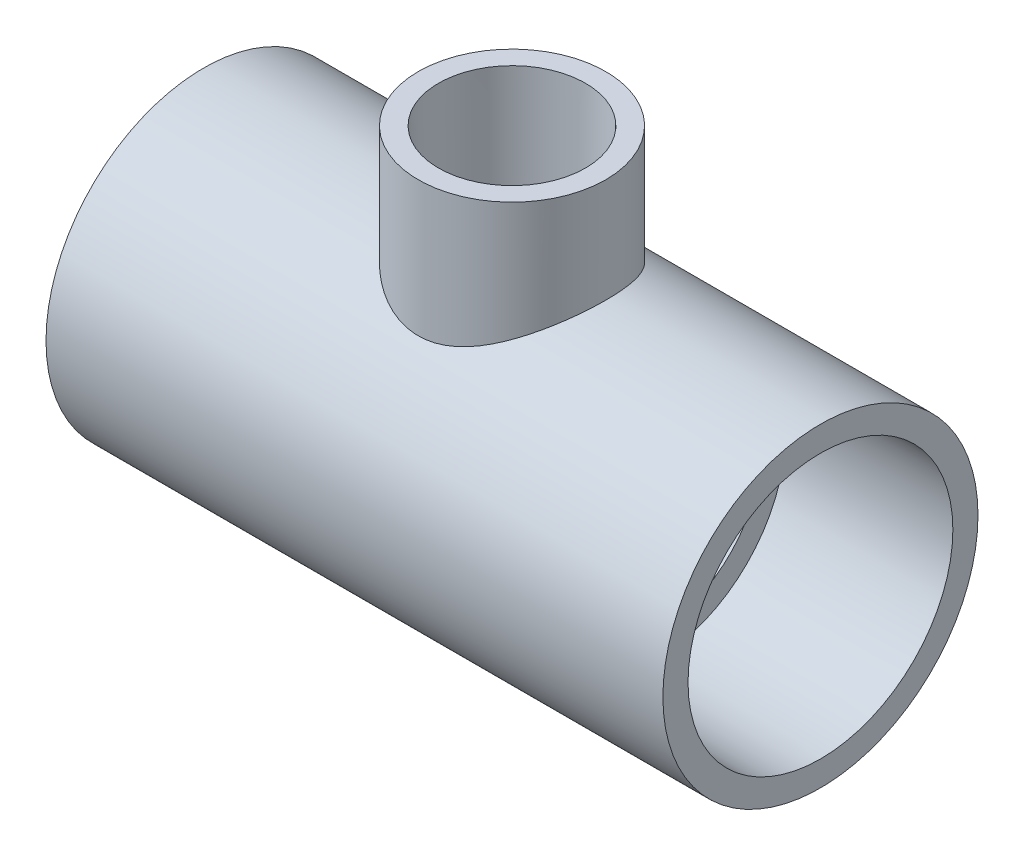
SolidWorks part; units mm, degrees
ref_plane "Front Plane" through (0, 0, 0) normal (0, 0, 1) x (1, 0, 0)
ref_plane "Top Plane" through (0, 0, 0) normal (0, 1, 0) x (1, 0, 0)
ref_plane "Right Plane" through (0, 0, 0) normal (1, 0, 0) x (0, 0, -1)
sketch "Sketch0" plane through (0, 0, 0) normal (0, 0, 1) x (1, 0, 0)
  line L0 (-70.612, 0) -> (0, 0) construction
  line L1 (0, 0) -> (0, 59.944) construction
  line L2 (-32.512, 0) -> (0, 0) construction
  line L3 (0, 0) -> (0, 31.369) construction
  line L4 (-70.612, 36.068) -> (-70.612, -36.068) construction
  line L5 (-32.512, 30.0863) -> (-70.612, 30.3149) construction
  line L6 (-32.512, 30.0863) -> (-32.512, -30.0863) construction
  line L7 (-32.512, -30.0863) -> (-70.612, -30.3149) construction
  line L8 (-70.612, 30.3149) -> (-70.612, -30.3149) construction
  line L9 (-21.463, 59.944) -> (21.463, 59.944) construction
  line L10 (-16.8275, 59.944) -> (16.8275, 59.944) construction
  line L11 (16.8275, 59.944) -> (16.637, 31.369) construction
  line L12 (16.637, 31.369) -> (-16.637, 31.369) construction
  line L13 (-16.637, 31.369) -> (-16.8275, 59.944) construction
  line L14 (-32.512, 24.6253) -> (-32.512, -24.6253) construction
  line L15 (-70.612, 0) -> (-32.512, 0) construction
  line L16 (0, 59.944) -> (0, 31.369) construction
  line L17 (0, 0) -> (32.512, 0) construction
  line L18 (-12.1539, 31.369) -> (12.1539, 31.369) construction
  line L19 (32.512, 0) -> (70.612, 0) construction
  dimension "D1" = 38.1
  dimension "H" = 70.612
  dimension "G" = 32.512
  dimension "M" = 72.136
  dimension "OD A" = 60.6298
  dimension "OD B" = 60.1726
  dimension "ID" = 49.2506
  dimension "H3" = 59.944
  dimension "G3" = 31.369
  dimension "M3" = 42.926
  dimension "D2" = 28.575
  dimension "OD A3" = 33.655
  dimension "OD B3" = 33.274
  dimension "ID3" = 24.3078
sketch "Sketch1" plane through (0, 0, 0) normal (0, 0, 1) x (1, 0, 0)
  line L0 (-70.612, 0) -> (0, 0) construction
  line L1 (-70.612, 0) -> (0, 0) construction
  line L2 (0, 0) -> (0, -36.068) construction
  line L3 (-70.612, -36.068) -> (-32.512, -36.068)
  line L4 (-70.612, -36.068) -> (-70.612, -30.3149)
  line L5 (-70.612, -30.3149) -> (-32.512, -30.0863)
  line L6 (-32.512, -36.068) -> (-32.512, -30.0863)
  line L7 (-32.512, -36.068) -> (0, -36.068) construction
  line L8 (70.612, -30.3149) -> (32.512, -30.0863)
  line L9 (70.612, -36.068) -> (70.612, -30.3149)
  line L10 (32.512, -36.068) -> (32.512, -30.0863)
  line L11 (70.612, -36.068) -> (32.512, -36.068)
revolve "Revolve1" add sketch "Sketch1" angle 360 about L1
sketch "Sketch2" plane through (0, 0, 0) normal (0, 0, 1) x (1, 0, 0)
  line L0 (16.8275, 59.944) -> (16.637, 31.369)
  line L1 (16.637, 31.369) -> (21.463, 31.369)
  line L2 (21.463, 31.369) -> (21.463, 59.944)
  line L3 (21.463, 59.944) -> (16.8275, 59.944)
  line L4 (0, 0) -> (0, 59.944) construction
  line L5 (0, 0) -> (0, 59.944) construction
revolve "Revolve2" add sketch "Sketch2" angle 360 about L5
sketch "Sketch3" plane through (-32.512, 0, 0) normal (1, 0, 0) x (0, 0, -1)
  circle A0 centre (0, 0) radius 24.6253
  circle A1 centre (0, 0) radius 36.068
sketch "Sketch4" plane through (-32.512, 0, 0) normal (1, 0, 0) x (0, 0, -1)
  circle A0 centre (0, 0) radius 36.068 construction
  circle A1 centre (0, 0) radius 36.068
extrude "Boss-Extrude1" add sketch "Sketch4" along normal up to vertex (65.024 mm away) up to point (32.512, 0, 0)
sketch "Sketch5" plane through (0, 31.369, 0) normal (0, -1, 0) x (1, 0, 0)
  circle A0 centre (0, 0) radius 21.463 construction
  circle A1 centre (0, 0) radius 21.463
extrude "Boss-Extrude2" add sketch "Sketch5" along normal up to vertex (31.369 mm away) up to point (0, 0, 0)
sketch "Sketch6" plane through (0, 0, 0) normal (0, 0, 1) x (1, 0, 0)
  line L0 (-70.612, -30.3149) -> (-32.512, -30.0863)
  line L1 (-32.512, -30.0863) -> (-32.512, -24.6253)
  line L2 (-32.512, -24.6253) -> (32.512, -24.6253)
  line L3 (32.512, -30.0863) -> (32.512, 30.0863) construction
  line L4 (0, -24.6253) -> (0, 0) construction
  line L5 (32.512, -30.0863) -> (32.512, -24.6253)
  line L6 (70.612, -30.3149) -> (70.612, 30.3149) construction
  line L7 (70.612, -36.068) -> (70.612, 36.068) construction
  line L8 (70.612, -30.3149) -> (70.612, 0)
  line L9 (70.612, 0) -> (-70.612, 0)
  line L10 (-70.612, 0) -> (-70.612, -30.3149)
  line L11 (70.612, -30.3149) -> (32.512, -30.0863)
revolve "Cut-Revolve1" cut sketch "Sketch6" angle 360 about L9
sketch "Sketch7" plane through (0, 0, 0) normal (0, 0, 1) x (1, 0, 0)
  line L0 (16.8275, 59.944) -> (16.637, 31.369)
  line L1 (16.637, 31.369) -> (12.1539, 31.369)
  line L2 (12.1539, 31.369) -> (12.1539, 0)
  line L3 (0, 0) -> (32.512, 0) construction
  line L4 (12.1539, 0) -> (0, 0)
  line L5 (0, 0) -> (0, 59.944)
  line L6 (-21.463, 59.944) -> (21.463, 59.944) construction
  line L7 (0, 59.944) -> (16.8275, 59.944)
revolve "Cut-Revolve2" cut sketch "Sketch7" angle 360 about L5
other "CPoint1" parameters "Diameter"=25.4, "StubLength"=38.1
ref_axis "Axis1" through (0, 41.369, 0) along (0, -1, 0)
other "CPoint2" parameters "Diameter"=50.8, "StubLength"=38.1
ref_axis "Axis2" through (-42.512, 0, 0) along (1, 0, 0)
other "CPoint3" parameters "Diameter"=50.8, "StubLength"=38.1
ref_axis "Axis3" through (42.512, 0, 0) along (-1, 0, 0)
other "RPoint1"
